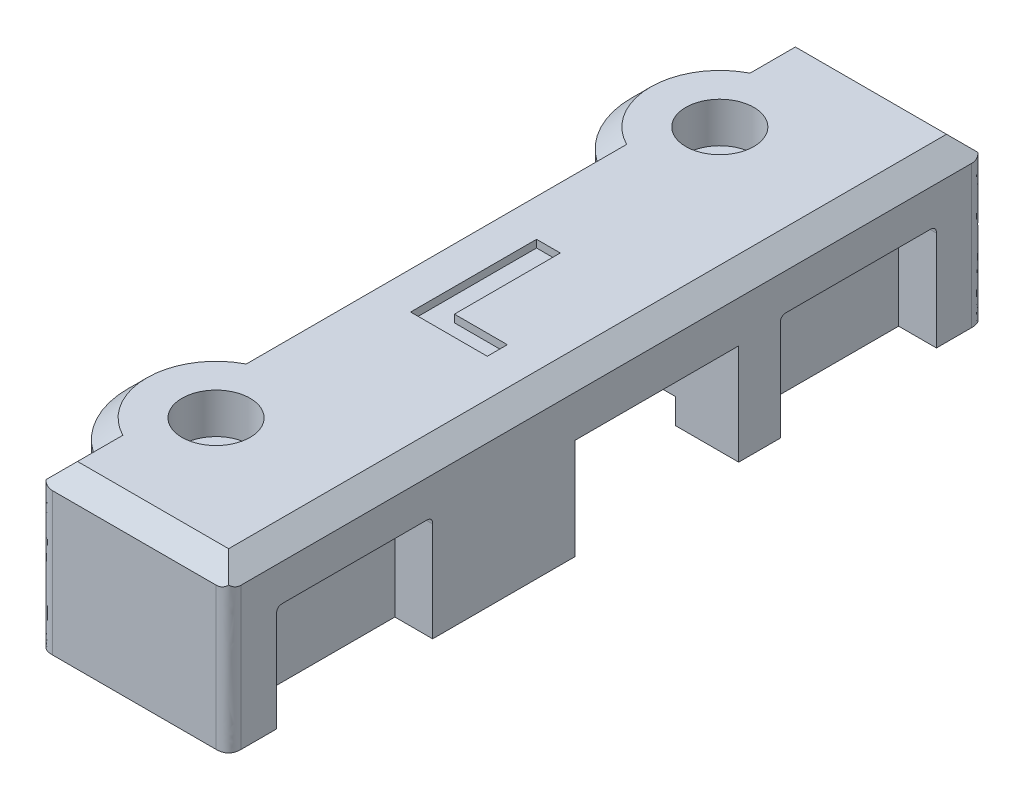
SolidWorks part; units mm, degrees
ref_plane "Front Plane" through (0, 0, 0) normal (0, 0, 1) x (1, 0, 0)
ref_plane "Top Plane" through (0, 0, 0) normal (0, 1, 0) x (1, 0, 0)
ref_plane "Right Plane" through (0, 0, 0) normal (1, 0, 0) x (0, 0, -1)
sketch "Sketch1" plane through (0, 0, 0) normal (0, 1, 0) x (1, 0, 0)
  line L0 (-1.3042, 0) -> (2.0884, 0) construction
  line L1 (0, -3.051) -> (0, -13.887) construction
  line L2 (7.5, 20) -> (-7.5, 20) construction
  line L3 (7.5, -30) -> (-7.5, -30)
  line L4 (7.5, -30) -> (7.5, 30)
  line L5 (7.5, 30) -> (-7.5, 30)
  line L6 (-7.5, -30) -> (-7.5, 30)
  line L7 (7.5, -30) -> (-7.5, 30) construction
  line L8 (7.5, 30) -> (-7.5, -30) construction
  line L9 (7.5, -20) -> (-7.5, -20) construction
  circle A6 centre (-3.5, 20) radius 1.65
  circle A7 centre (-3.5, -20) radius 1.65
  point P3 (0, 0)
  dimension "D4" = 3.3
  dimension "D1" = 10
  dimension "D2" = 40
  dimension "D3" = 15
  dimension "D5" = 4
extrude "Boss-Extrude1" add sketch "Sketch1" along normal blind 12.8
sketch "Sketch5" plane through (0, 0, 0) normal (0, -1, 0) x (1, 0, 0)
  line L0 (7.5, -30) -> (-7.5, -30) construction
  line L1 (-5.5, -10.5) -> (7.5, -10.5)
  line L2 (-5.5, -10.5) -> (-5.5, 2.5)
  line L3 (-5.5, 2.5) -> (7.5, 2.5)
  line L4 (7.5, -10.5) -> (7.5, 2.5)
  line L8 (7.5, 30) -> (7.5, -30) construction
  dimension "D1" = 13
  dimension "D2" = 13
  dimension "D3" = 19.5
extrude "Cut-Extrude3" cut sketch "Sketch5" against normal blind 8 and the other way through all
sketch "Sketch6" plane through (0, 8, 0) normal (0, -1, 0) x (1, 0, 0)
  line L0 (-7.5, -4) -> (7.5, -4) construction
  line L3 (7.5, -10.5) -> (7.5, 2.5) construction
  line L4 (-7.5, -30) -> (-7.5, 30) construction
  circle A0 centre (2.5, -0.75) radius 1.45
  circle A1 centre (2.5, -7.25) radius 1.45
  dimension "D1" = 2.9
  dimension "D2" = 5
  dimension "D3" = 6.5
extrude "Cut-Extrude4" cut sketch "Sketch6" against normal blind 3
sketch "Sketch8" plane through (0, 12.8, 0) normal (0, 1, 0) x (1, 0, 0)
  circle A0 centre (-3.5, 20) radius 2.7
  circle A1 centre (-3.5, -20) radius 2.7
  dimension "D1" = 5.4
extrude "Cut-Extrude6" cut sketch "Sketch8" against normal blind 3.2
sketch "Sketch9" plane through (0, 0, 0) normal (0, -1, 0) x (1, 0, 0)
  line L6 (-5.5, -10.5) -> (7.5, -10.5) construction
  line L7 (2.5, -10.5) -> (-1.5, -10.5)
  line L8 (2.5, -10.5) -> (2.5, -30)
  line L9 (2.5, -30) -> (-1.5, -30)
  line L10 (-1.5, -10.5) -> (-1.5, -30)
  line L11 (7.5, -30) -> (-7.5, -30) construction
  circle A1 centre (-3.5, -20) radius 1.65 construction
  dimension "D3" = 4
  dimension "D4" = 2
extrude "Cut-Extrude7" cut sketch "Sketch9" against normal blind 2
sketch "Sketch10" plane through (7.5, 0, 0) normal (1, 0, 0) x (0, 0, -1)
  line L0 (0, 0) -> (0, 24.8288) construction
  line L1 (10.5, 0) -> (30, 0) construction
  line L2 (-26.2, 0) -> (-13.8, 0)
  line L3 (-26.2, 0) -> (-26.2, 8.4)
  line L4 (-26.2, 8.4) -> (-13.8, 8.4)
  line L5 (-13.8, 0) -> (-13.8, 8.4)
  line L6 (-26.2, 0) -> (-13.8, 8.4) construction
  line L7 (-26.2, 8.4) -> (-13.8, 0) construction
  line L8 (13.8, 0) -> (26.2, 0)
  line L9 (13.8, 0) -> (13.8, 8.4)
  line L10 (13.8, 8.4) -> (26.2, 8.4)
  line L11 (26.2, 0) -> (26.2, 8.4)
  line L12 (13.8, 0) -> (26.2, 8.4) construction
  line L13 (13.8, 8.4) -> (26.2, 0) construction
  line L14 (-30, 0) -> (-2.5, 0) construction
  point P1 (-20, 4.2)
  point P9 (20, 4.2)
  dimension "D1" = 12.4
  dimension "D2" = 8.4
  dimension "D3" = 40
extrude "Cut-Extrude8" cut sketch "Sketch10" against normal blind 3
sketch "Sketch11" plane through (0, 12.8, 0) normal (0, 1, 0) x (1, 0, 0)
  line L0 (0, 30) -> (0, -30) construction
  line L1 (7.5, 30) -> (-7.5, 30) construction
  line L2 (-7.5, -30) -> (7.5, -30) construction
  line L3 (-7.5, 0) -> (7.5, 0) construction
  line L4 (-7.5, 30) -> (-7.5, -30) construction
  line L5 (7.5, -30) -> (7.5, 30) construction
  text T0 "L" font "Consolas" height 10
  dimension "D1" = 4.5
  dimension "D2" = 5
extrude "Cut-Extrude9" cut sketch "Sketch11" against normal blind 0.6
fillet "Fillet1" radius 0.5 4 edges at (6, 8.4, 26.2) (6, 8.4, 13.8) (6, 8.4, -13.8) (6, 8.4, -26.2) conic rho 0.5
sketch "Sketch12" plane through (0, 0, 0) normal (0, 1, 0) x (1, 0, 0)
  line L0 (-7.5, 30) -> (-7.5, -30) construction
  line L1 (16.6697, 0) -> (-21.1051, 0) construction
  line L2 (-7.5, 25.7446) -> (-7.5, 14.2554)
  line L3 (-7.5, -25.7446) -> (-7.5, -14.2554)
  arc A0 (-7.5, 14.2554) -> (-7.5, 25.7446) centre (-3.5, 20) cw
  arc A1 (-7.5, -14.2554) -> (-7.5, -25.7446) centre (-3.5, -20) ccw
  dimension "D1" = 7
extrude "Boss-Extrude2" add sketch "Sketch12" along normal up to surface (12.8 mm away) up to face at (-3.5, 12.8, -17.3)
chamfer "Chamfer2" distance 1.5 angle 45 8 edges at (0, 12.8, 30) (-7.5, 12.8, 27.8723) (-10.5, 12.8, 20) (7.5, 12.8, 0) (0, 12.8, -30) (-7.5, 12.8, -27.8723) (-10.5, 12.8, -20) (-7.5, 12.8, 0)
fillet "Fillet3" radius 1 4 edges at (-7.5, 5.65, -30) (7.5, 5.65, -30) (7.5, 5.65, 30) (-7.5, 5.65, 30) conic rho 0.5
chamfer "Chamfer3" distance 0.6 angle 45 2 edges at (2.5, 8, -5.8) (2.5, 8, -2.2)
